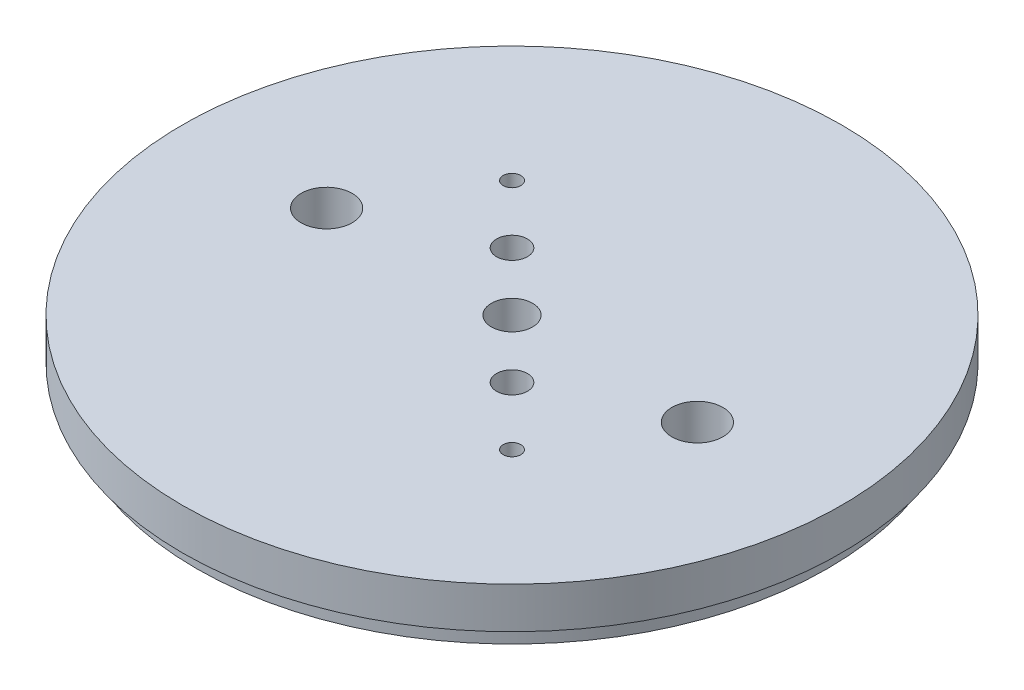
SolidWorks part; units mm, degrees
material "6061-T4 (SS)"
ref_plane "Front Plane" through (0, 0, 0) normal (0, 0, 1) x (1, 0, 0)
ref_plane "Top Plane" through (0, 0, 0) normal (0, 1, 0) x (1, 0, 0)
ref_plane "Right Plane" through (0, 0, 0) normal (1, 0, 0) x (0, 0, -1)
sketch "Sketch1" plane through (0, 0, 0) normal (0, 1, 0) x (1, 0, 0)
  line L0 (0, -50.8) -> (0, 50.8) construction
  line L1 (-50.8, 0) -> (50.8, 0) construction
  line L2 (-17.9605, 17.9605) -> (0, 0) construction
  line L3 (0, 56.7387) -> (0, 29.6936) construction
  line L4 (3.6407, 56.7387) -> (3.6407, 29.6936) construction
  line L5 (-3.6407, 56.7387) -> (-3.6407, 29.6936) construction
  line L6 (0, -56.7387) -> (0, -29.6936) construction
  line L7 (3.6407, -56.7387) -> (3.6407, -29.6936) construction
  line L8 (-3.6407, -56.7387) -> (-3.6407, -29.6936) construction
  line L9 (-35.921, -35.921) -> (54.3236, 54.3236) construction
  circle A0 centre (0, 0) radius 50.8
  circle A1 centre (0, 0) radius 3.175
  circle A2 centre (28.575, 0) radius 3.937
  circle A3 centre (-28.575, 0) radius 3.937
  circle A4 centre (-17.9605, 17.9605) radius 1.3589
  arc A6 (3.6407, 56.7387) -> (-3.6407, 56.7387) centre (0, 56.7387) ccw construction
  arc A7 (-3.6407, 29.6936) -> (3.6407, 29.6936) centre (0, 29.6936) ccw construction
  arc A8 (3.6407, -56.7387) -> (-3.6407, -56.7387) centre (0, -56.7387) cw construction
  arc A9 (-3.6407, -29.6936) -> (3.6407, -29.6936) centre (0, -29.6936) cw construction
  circle A10 centre (17.9605, -17.9605) radius 1.3589
  circle A11 centre (-8.9803, 8.9803) radius 2.3813
  circle A12 centre (8.9803, -8.9803) radius 2.3813
  point P16 (0, 43.2162)
  point P19 (0, 0)
  point P26 (0, -43.2162)
  point P35 (0, 0)
  point P36 (0, 0)
  dimension "D1" = 101.6
  dimension "D2" = 6.35
  dimension "D3" = 7.874
  dimension "D5" = 2.7178
  dimension "D8" = 4.7625
  dimension "D4" = 45
  dimension "D6" = 25.4
  dimension "D7" = 45
  dimension "D9" = 28.575
extrude "Boss-Extrude1" add sketch "Sketch1" along normal blind 9.525
sketch "Sketch2" plane through (0, 0, 0) normal (0, -1, 0) x (1, 0, 0)
  circle A0 centre (0, 0) radius 50.8
  circle A1 centre (0, 0) radius 48.641
  dimension "D1" = 101.6
  dimension "D2" = 97.282
extrude "Cut-Extrude1" cut sketch "Sketch2" against normal blind 3.175
sketch "Sketch3" plane through (0, 9.525, 0) normal (0, 1, 0) x (1, 0, 0)
  line L0 (0, 50.8) -> (0, -50.8) construction
  line L1 (-50.8, 0) -> (50.8, 0) construction
  line L2 (0, 34.798) -> (0, 13.97) construction
  line L3 (3.2385, 34.798) -> (3.2385, 13.97)
  line L4 (-3.2385, 34.798) -> (-3.2385, 13.97)
  line L5 (0, -34.798) -> (0, -13.97) construction
  line L6 (3.2385, -34.798) -> (3.2385, -13.97)
  line L7 (-3.2385, -34.798) -> (-3.2385, -13.97)
  circle A0 centre (0, 0) radius 50.8 construction
  arc A1 (3.2385, 34.798) -> (-3.2385, 34.798) centre (0, 34.798) ccw
  arc A2 (-3.2385, 13.97) -> (3.2385, 13.97) centre (0, 13.97) ccw
  arc A3 (3.2385, -34.798) -> (-3.2385, -34.798) centre (0, -34.798) cw
  arc A4 (-3.2385, -13.97) -> (3.2385, -13.97) centre (0, -13.97) cw
  point P7 (0, 13.97)
  point P8 (0, 34.798)
  point P12 (0, 24.384)
  point P17 (0, 0)
  point P20 (0, -24.384)
  point P25 (0, -34.798)
  point P26 (0, -13.97)
  dimension "D1" = 13.97
  dimension "D2" = 20.828
  dimension "D3" = 6.477
extrude "Cut-Extrude2" cut sketch "Sketch3" against normal blind 3.556 from offset 5.969 offset against normal yes
equation "\"leadDist\"=1.5"
